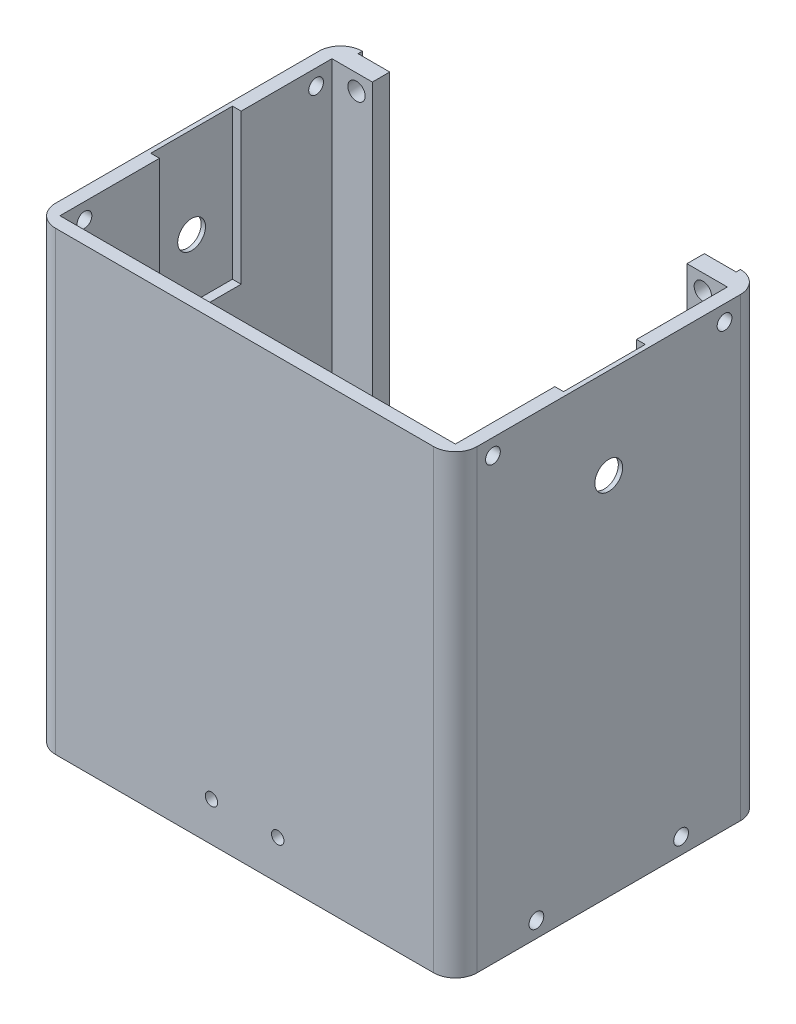
SolidWorks part; units mm, degrees
ref_plane "Front Plane" through (0, 0, 0) normal (0, 0, 1) x (1, 0, 0)
ref_plane "Top Plane" through (0, 0, 0) normal (0, 1, 0) x (1, 0, 0)
ref_plane "Right Plane" through (0, 0, 0) normal (1, 0, 0) x (0, 0, -1)
sketch "Sketch1" plane through (0, 0, 0) normal (0, 1, 0) x (1, 0, 0)
  line L0 (-43.5, 32.3) -> (43.5, 32.3) construction
  line L1 (-43.5, -35.3) -> (43.5, -35.3)
  line L2 (-48.5, -30.3) -> (-48.5, 30.3)
  line L3 (-43.5, 35.3) -> (43.5, 35.3)
  line L31 (48.5, -30.3) -> (48.5, 30.3)
  line L32 (-48.5, -35.3) -> (48.5, 35.3) construction
  line L33 (-48.5, 35.3) -> (48.5, -35.3) construction
  line L34 (45.5, -30.3) -> (45.5, 30.3)
  line L35 (-43.5, -32.3) -> (43.5, -32.3)
  line L36 (-45.5, -30.3) -> (-45.5, 30.3)
  line L37 (-43.5, 35.3) -> (-43.5, 32.3)
  line L38 (43.5, 35.3) -> (43.5, 32.3)
  line L39 (-43.5, 34.3) -> (-36.2, 34.3)
  line L40 (-36.2, 34.3) -> (-36.2, 30.3)
  line L41 (-36.2, 30.3) -> (-45.5, 30.3)
  line L42 (0, 35.3) -> (0, 0) construction
  line L43 (43.5, 34.3) -> (36.2, 34.3)
  line L44 (36.2, 34.3) -> (36.2, 30.3)
  line L45 (36.2, 30.3) -> (45.5, 30.3)
  line L46 (-36.2, 30.3) -> (-36.2, -32.3)
  line L47 (36.2, 30.3) -> (36.2, -32.3)
  line L48 (-36.2, 34.3) -> (36.2, 34.3)
  line L49 (-45.5, -30.3) -> (-45.5, -32.3)
  line L50 (-45.5, -32.3) -> (-43.5, -32.3)
  line L51 (43.5, -32.3) -> (45.5, -32.3)
  line L52 (45.5, -32.3) -> (45.5, -30.3)
  arc A17 (-43.5, -35.3) -> (-48.5, -30.3) centre (-43.5, -30.3) cw
  arc A18 (43.5, -35.3) -> (48.5, -30.3) centre (43.5, -30.3) ccw
  arc A19 (43.5, 35.3) -> (48.5, 30.3) centre (43.5, 30.3) cw
  arc A20 (-48.5, 30.3) -> (-43.5, 35.3) centre (-43.5, 30.3) cw
  arc A21 (43.5, 32.3) -> (45.5, 30.3) centre (43.5, 30.3) cw
  arc A22 (43.5, -32.3) -> (45.5, -30.3) centre (43.5, -30.3) ccw
  arc A23 (-43.5, -32.3) -> (-45.5, -30.3) centre (-43.5, -30.3) cw
  arc A24 (-45.5, 30.3) -> (-43.5, 32.3) centre (-43.5, 30.3) cw
  point P0 (0, 0)
  dimension "D1" = 70.6
  dimension "D2" = 97
  dimension "D3" = 5
  dimension "D4" = 3
  dimension "D5" = 1
  dimension "D6" = 4
  dimension "D7" = 7.3
extrude "Boss-Extrude1" add sketch "Sketch1" along normal blind 104.887 contours L36 A24 L37 A20 L2 A17 L1 A18 L31 A19 L38 A21 L34 A22 L35 A23 | A24 L41 L40 L39 L37 | A21 L38 L43 L44 L45 region at (-46.1872, 0, 32.9872) region at (-40.287, 0, -32.1882) region at (40.287, 0, -32.1882)
sketch "Sketch2" plane through (48.5, 0, 0) normal (1, 0, 0) x (0, 0, -1)
  line L0 (16.65, 0) -> (16.65, 3.65) construction
  line L1 (-30.3, 0) -> (30.3, 0) construction
  line L2 (16.65, 3.65) -> (30.3, 3.65) construction
  line L4 (-30.3, 0) -> (30.3, 0) construction
  line L5 (0, 0) -> (0, 104.887) construction
  line L6 (-30.3, 104.887) -> (30.3, 104.887) construction
  line L7 (30.3, 104.887) -> (30.3, 0) construction
  line L8 (-30.3, 3.65) -> (-16.65, 3.65) construction
  line L9 (-30.3, 104.887) -> (-30.3, 0) construction
  line L10 (-16.65, 3.65) -> (-16.65, 0) construction
  circle A0 centre (16.65, 3.65) radius 1.7
  circle A1 centre (-16.65, 3.65) radius 1.7
  dimension "D3" = 3.4
  dimension "D4" = 3.4
  dimension "D1" = 13.65
  dimension "D2" = 3.65
  dimension "D5" = 13.65
extrude "Cut-Extrude1" cut sketch "Sketch2" against normal through all
sketch "Sketch6" plane through (48.5, 0, 0) normal (1, 0, 0) x (0, 0, -1)
  line L0 (-26.65, 104.887) -> (-26.65, 101.237) construction
  line L1 (-30.3, 104.887) -> (30.3, 104.887) construction
  line L2 (-26.65, 101.237) -> (-30.3, 101.237) construction
  line L3 (-30.3, 104.887) -> (-30.3, 0) construction
  circle A0 centre (-26.65, 101.237) radius 1.7
  dimension "D1" = 3.4
  dimension "D2" = 3.65
  dimension "D3" = 3.65
extrude "Cut-Extrude9" cut sketch "Sketch6" against normal through all contours A0
ref_plane "Plane1" through (0, 52.4435, 0) normal (0, -1, 0) x (-1, 0, 0)
sketch "Sketch3" plane through (-48.5, 0, 0) normal (-1, 0, 0) x (0, 0, 1)
  line L0 (0, 104.887) -> (35.3, 104.887) construction
  line L1 (5.2, 90.287) -> (5.2, 77.687)
  line L2 (5.2, 90.287) -> (-5.2, 90.287)
  line L3 (-5.2, 90.287) -> (-5.2, 77.687)
  line L4 (5.2, 77.687) -> (-5.2, 77.687)
  line L5 (5.2, 90.287) -> (-5.2, 77.687) construction
  line L6 (-5.2, 90.287) -> (5.2, 77.687) construction
  line L7 (30.3, 104.887) -> (-30.3, 104.887) construction
  line L8 (-5.2, 77.687) -> (-9.4, 77.687)
  line L9 (0, 104.887) -> (0, 83.987) construction
  line L10 (-9.4, 77.687) -> (-9.4, 104.887)
  line L11 (0, 88.487) -> (0, 79.487) construction
  line L12 (0, 83.987) -> (5.2, 83.987) construction
  line L13 (-9.4, 104.887) -> (-5.2, 104.887)
  line L14 (-5.2, 104.887) -> (-5.2, 90.287)
  line L15 (5.2, 104.887) -> (5.2, 90.287)
  line L16 (9.4, 104.887) -> (5.2, 104.887)
  line L17 (9.4, 77.687) -> (9.4, 104.887)
  line L18 (5.2, 77.687) -> (9.4, 77.687)
  line L19 (-9.4, 77.687) -> (-9.4, 70.387)
  line L20 (-9.4, 70.387) -> (9.4, 70.387)
  line L21 (9.4, 70.387) -> (9.4, 77.687)
  circle A0 centre (0, 83.987) radius 32.5 construction
  circle A1 centre (0, 79.487) radius 1
  circle A2 centre (0, 88.487) radius 1
  circle A3 centre (0, 83.987) radius 3.2
  point P0 (0, 83.987)
  line M70 (30.3, 104.887) -> (-30.3, 104.887)
  dimension "D3" = 65
  dimension "D5" = 2
  dimension "D7" = 6.4
  dimension "D1" = 12.6
  dimension "D2" = 10.4
  dimension "D4" = 14.6
  dimension "D6" = 4.5
  dimension "D8" = 4.2
  dimension "D9" = 7.3
mirror "Mirror11" about plane through (0, 0, 0) normal (0, 0, 1) of "Cut-Extrude9"
extrude "Cut-Extrude4" cut sketch "Sketch3<9>" against normal through all contours A3 region at (-48.5, 83.987, 0)
sketch "Sketch3<9>" plane through (-48.5, 0, 0) normal (-1, 0, 0) x (0, 0, 1) same geometry as "Sketch3"
sketch "Sketch4" plane through (0, 0, -34.3) normal (0, 0, -1) x (-1, 0, 0)
  line L0 (43.5, 104.887) -> (43.5, 0) construction
  line L1 (36.2, 0) -> (43.5, 0) construction
  line L2 (36.2, 0) -> (36.2, 7.3) construction
  line L3 (36.2, 7.3) -> (43.5, 7.3) construction
  line L4 (43.5, 0) -> (43.5, 7.3) construction
  line L5 (39.85, 7.3) -> (39.85, 0) construction
  circle A0 centre (39.85, 3.65) radius 2
  dimension "D2" = 4
  dimension "D1" = 7.3
extrude "Cut-Extrude5" cut sketch "Sketch4" against normal blind 4
mirror "Mirror7" about plane through (0, 0, 0) normal (1, 0, 0) of "Cut-Extrude5"
sketch "Sketch5" plane through (0, 0, 35.3) normal (0, 0, 1) x (1, 0, 0)
  line L0 (0, -3) -> (0, 21.1) construction
  line L1 (0, 9.05) -> (-7.625, 9.05) construction
  circle A0 centre (-7.625, 9.05) radius 1.43
  circle A1 centre (7.625, 9.05) radius 1.43
  dimension "D3" = 2.86
  dimension "D1" = 24.1
  dimension "D2" = 7.625
  dimension "D4" = 3
extrude "Cut-Extrude6" cut sketch "Sketch5" against normal through all
ref_plane "Plane3" through (0, 52.4435, 0) normal (0, 1, 0) x (1, 0, 0)
mirror "Mirror9" about plane through (0, 52.4435, 0) normal (0, 1, 0) of "Mirror7", "Cut-Extrude5"
extrude "Cut-Extrude7" cut sketch "Sketch3<10>" along normal blind 2 from surface contours L14 L10 L8 L3 M70 | L1 L18 L17 L15 M70 | L15 L14 L2 M70 | L20 L21 L18 L4 L8 L19 | L4 L1 L2 L3 A3 A1 A2 | A1 | A3 | A2 region at (-48.5, 91.287, 7.3) region at (-48.5, 83.987, 5.0366) region at (-48.5, 97.587, 0) region at (-48.5, 74.037, 0) region at (-48.5, 91.287, -7.3) region at (-48.5, 79.487, 0) region at (-48.5, 88.487, 0) region at (-48.5, 83.987, 0) starting at face at (-45.5, 83.987, 3.2)
sketch "Sketch3<10>" plane through (-48.5, 0, 0) normal (-1, 0, 0) x (0, 0, 1) same geometry as "Sketch3"
extrude "Cut-Extrude8" cut sketch "Sketch3" against normal blind 2 from surface contours L14 L10 L8 L3 M70 | L1 L18 L17 L15 M70 | L15 L14 L2 M70 | L4 L1 L2 L3 A3 A1 A2 | A2 | A3 | A1 | L20 L21 L18 L4 L8 L19 region at (-48.5, 91.287, 7.3) region at (-48.5, 83.987, 5.0366) region at (-48.5, 97.587, 0) region at (-48.5, 74.037, 0) region at (-48.5, 91.287, -7.3) region at (-48.5, 79.487, 0) region at (-48.5, 88.487, 0) region at (-48.5, 83.987, 0) starting at face at (45.5, 83.987, 3.2)
sketch "Sketch7" plane through (0, 104.887, 0) normal (0, 1, 0) x (1, 0, 0)
  line L0 (0, -35.3) -> (0, 35.3) construction
  line L1 (-43.5, -35.3) -> (43.5, -35.3) construction
  line L2 (43.5, 35.3) -> (0, 35.3) construction
  line L3 (48.5, -30.3) -> (48.5, 30.3) construction
  line L4 (-48.5, 35.3) -> (48.5, 35.3)
  line L5 (-48.5, 35.3) -> (-48.5, -35.3)
  line L6 (-48.5, -35.3) -> (48.5, -35.3)
  line L7 (48.5, 35.3) -> (48.5, -35.3)
  line L8 (-48.5, 35.3) -> (48.5, -35.3) construction
  line L9 (-48.5, -35.3) -> (48.5, 35.3) construction
  point P6 (0, 0)
extrude "Cut-Extrude10" [suppressed] cut sketch "Sketch7" against normal blind 0.4
